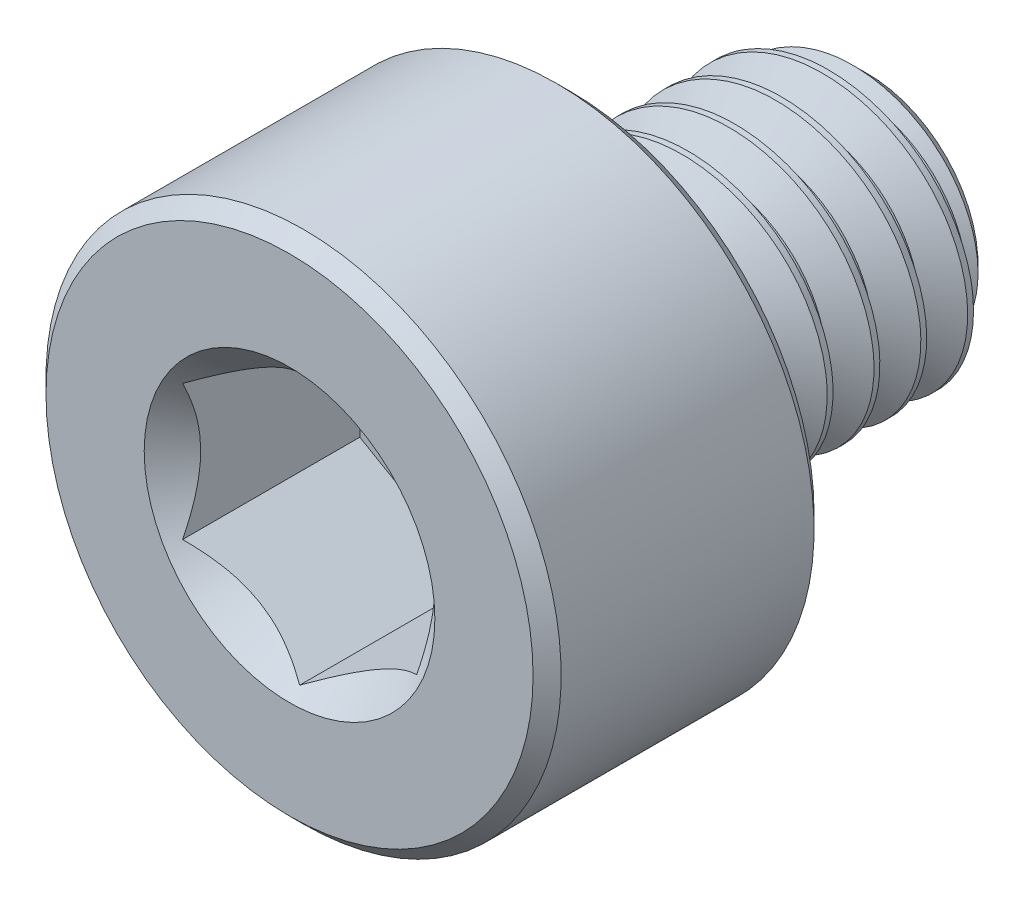
SolidWorks part; units mm, degrees
ref_plane "Front Plane" through (0, 0, 0) normal (0, 0, 1) x (1, 0, 0)
ref_plane "Top Plane" through (0, 0, 0) normal (0, 1, 0) x (1, 0, 0)
ref_plane "Right Plane" through (0, 0, 0) normal (1, 0, 0) x (0, 0, -1)
sketch "Sketch1" plane through (0, 0, 0) normal (1, 0, 0) x (0, 0, -1)
  line L0 (-3.0875, 0) -> (3.0875, 0) construction
  line L1 (3.0875, 0) -> (3.0875, 1.1752) construction
  line L2 (3.0875, 1.1752) -> (2.7627, 1.5) construction
  line L3 (2.7627, 1.5) -> (2.7125, 1.5) construction
  line L4 (2.7125, 1.5) -> (-0.0875, 1.5) construction
  line L5 (-0.0875, 1.5) -> (-0.0875, 2.75) construction
  line L6 (-0.0875, 2.75) -> (-3.0875, 2.75) construction
  line L7 (-3.0875, 2.75) -> (-3.0875, 0) construction
  line L8 (3.0875, 1.1752) -> (3.0875, 1.5) construction
  line L9 (3.0563, 1.5541) -> (3.3063, 1.1211) construction
  line L10 (3.3063, 1.1211) -> (3.5563, 1.5541) construction
  line L11 (3.5563, 1.5541) -> (3.0563, 1.5541) construction
  line L12 (3.3063, 1.5541) -> (3.3063, 1.5) construction
  line L13 (3.3063, 1.1211) -> (3.3063, 1.1752) construction
  line L14 (3.275, 1.1752) -> (3.3375, 1.1752) construction
  line L15 (3.0875, 1.5) -> (3.525, 1.5) construction
  line L16 (3.0719, 1.5271) -> (3.5406, 1.5271) construction
  line L17 (3.0875, 0) -> (3.0875, -1.5) construction
  line L18 (-0.2375, 2.75) -> (-0.0875, 2.6) construction
  line L19 (-2.9375, 2.75) -> (-3.0875, 2.6) construction
  line L20 (-0.0875, 1.5) -> (-0.0875, 0) construction
  line L21 (-0.0875, 0.75) -> (0.9708, 0.75) construction
  line L22 (0.9708, 0.75) -> (2.0292, 0.75) construction
  line L23 (2.0292, 0.75) -> (3.0875, 0.75) construction
  line L24 (0.9708, 0.75) -> (0.9708, 1.5) construction
  line L25 (0.9708, 1.5) -> (0.9708, 2.75) construction
  line L26 (2.0292, 0.75) -> (2.0292, 2.75) construction
  point P0 (-3.0875, 1.25)
  point P3 (1.8375, 1.5)
  point P4 (0, 0)
  point P18 (2.0292, 1.5)
  point P22 (3.3063, 1.1752)
  point P24 (2.7125, 1.5)
  point P25 (3.3063, 1.5)
  point P28 (3.3062, 1.5271)
  point P29 (1.8375, -1.5)
  point P30 (0.9708, 1.5)
  point P31 (-1.5875, 2.75)
  point P37 (-0.6125, 2.75)
  point P38 (-2.8625, 2.75)
  point P45 (0.9708, 0.75)
  point P46 (2.0292, 0.75)
  dimension "D2" = 0.0625
  dimension "D7" = 0.15
  dimension "D8" = 0.15
  dimension "D9" = 0.15
  dimension "D10" = 0.075
  dimension "D11" = 0.375
  dimension "Drive Size" = 2.5
  dimension "Head Diameter" = 5.5
  dimension "Head Height" = 3
  dimension "Thread Pitch" = 0.5
  dimension "Thread Dia" = 3
  dimension "Length" = 3.175
  dimension "D12" = 0.375
  dimension "D4" = 1.25
  dimension "D3" = 45
sketch "Sketch2" plane through (0, 0, 0) normal (1, 0, 0) x (0, 0, -1)
  line L0 (-3.0875, 0) -> (-3.0875, 2.6)
  line L1 (-2.9375, 2.75) -> (-0.2375, 2.75)
  line L2 (-0.0875, 2.6) -> (-0.0875, 1.65)
  line L4 (2.7627, 1.5) -> (3.0875, 1.1752)
  line L5 (3.0875, 1.1752) -> (3.0875, 0)
  line L6 (-0.0875, 2.75) -> (-3.0875, 2.75) construction
  line L7 (3.0875, 0) -> (-3.0875, 0)
  line L8 (-2.9375, 2.75) -> (-3.0875, 2.6) construction
  line L10 (-2.9375, 2.75) -> (-3.0875, 2.6)
  line L14 (-0.2375, 2.75) -> (-0.0875, 2.6) construction
  line L16 (-0.2375, 2.75) -> (-0.0875, 2.6)
  line L17 (-0.0875, 1.5) -> (-0.0875, 2.75) construction
  line L19 (0.0625, 1.5) -> (2.7627, 1.5)
  line L20 (2.7125, 1.5) -> (-0.0875, 1.5) construction
  arc A1 (-0.0875, 1.65) -> (0.0625, 1.5) centre (0.0625, 1.65) ccw
  dimension "D3" = 0.15
revolve "Revolve1" add sketch "Sketch2" angle 360 about L7
sketch "Sketch3" plane through (0, 0, 3.0875) normal (0, 0, 1) x (1, 0, 0)
  line L1 (1.25, -0.7217) -> (1.25, 0.7217)
  line L2 (1.25, 0.7217) -> (0, 1.4434)
  line L3 (0, 1.4434) -> (-1.25, 0.7217)
  line L4 (-1.25, 0.7217) -> (-1.25, -0.7217)
  line L5 (-1.25, -0.7217) -> (0, -1.4434)
  line L6 (0, -1.4434) -> (1.25, -0.7217)
  circle A0 centre (0, 0) radius 1.25 construction
  circle A1 centre (0, 0) radius 2.75 construction
  circle A2 centre (0, 0) radius 2.75 construction
  circle A3 centre (0, 0) radius 1.4434 construction
  point P13 (0, 0)
  dimension "D1" = 2.8868
extrude "Cut-Extrude1" cut sketch "Sketch3" against normal offset from surface (2 mm away) 1 up to face at (0, 2.6, 0.0875)
sketch "Sketch4" plane through (0, 0, 3.0875) normal (0, 0, 1) x (1, 0, 0)
  circle A0 centre (0, 0) radius 1.5516
  dimension "D1" = 3.1033
extrude "Cut-Extrude2" cut sketch "Sketch4" against normal up to vertex (1.5 mm away) draft 45 up to point (0, 2.75, 1.5875)
sketch "Sketch11" plane through (0, 0, 0) normal (1, 0, 0) x (0, 0, -1)
  line L0 (-3.0875, 0) -> (3.0875, 0) construction
  line L1 (-3.0875, 0) -> (3.0875, 0) construction
  line L2 (0.5078, 0) -> (0.5078, 1.5) construction
  line L3 (2.7125, 1.5) -> (-0.0875, 1.5) construction
  line L4 (2.4922, 0) -> (2.4922, 1.5) construction
  line L6 (3.0875, 1.1752) -> (3.0875, 1.5) construction
  point P2 (0.5078, 0)
  point P3 (2.4922, 0)
  dimension "D1" = 0.5953
  dimension "D2" = 0.5953
sketch "Sketch6" plane through (0, 0, -3.0875) normal (0, 0, -1) x (-1, 0, 0)
  circle A0 centre (0, 0) radius 1.5
curve "Helix/Spiral1" pitch 0.5 height 3.675 radius 1.5 centre (0, 0, -3.0875) axis (0, 0, 1) start towards (0, 1, 0)
sketch "Sketch10" plane through (0, 0, 0) normal (1, 0, 0) x (0, 0, -1)
  line L0 (0.0625, -2.75) -> (0.0625, 2.75)
  line L5 (-3.0875, 0) -> (3.0875, 0) construction
  line L6 (0.0625, 1.5) -> (0.0625, -1.5) construction
  point P3 (0.0625, 0)
split "Split1" trim tools "Sketch10" bodies to split 106 resulting bodies 114 115
sketch "Sketch7" plane through (0, 0, 0) normal (1, 0, 0) x (0, 0, -1)
  line L0 (3.0719, 1.5271) -> (3.5406, 1.5271)
  line L1 (3.5406, 1.5271) -> (3.3375, 1.1752)
  line L2 (3.3375, 1.1752) -> (3.275, 1.1752)
  line L3 (3.275, 1.1752) -> (3.0719, 1.5271)
sweep "Cut-Sweep1" cut profiles "Sketch7" path "Helix/Spiral1" align with end faces yes
sketch "Sketch8" plane through (0, 0, 0) normal (1, 0, 0) x (0, 0, -1)
  line L0 (-0.0875, 0) -> (-0.0875, 1.5)
  line L1 (0.0625, -1.5) -> (0.0625, 1.5) construction
  line L2 (-0.0875, 1.5) -> (0.0625, 1.5)
  line L4 (0.0625, 1.5) -> (0.9285, 0)
  line L5 (0.9285, 0) -> (-0.0875, 0)
  line L6 (2.7125, 1.5) -> (-0.0875, 1.5) construction
  line L7 (-3.0875, 0) -> (3.0875, 0) construction
  dimension "D1" = 60
revolve "Revolve2" add sketch "Sketch8" angle 360 about L5
equation "\"D2@Sketch1\" = \"Thread Pitch@Sketch1\" / 8"
equation "\"D4@Helix/Spiral1\" = \"Thread Pitch@Sketch1\""
equation "\"D7@Sketch1\" = \"Head Height@Sketch1\" * .05"
equation "\"D8@Sketch1\"=\"D7@Sketch1\""
equation "\"D9@Sketch1\"=\"D7@Sketch1\""
equation "\"D10@Sketch1\"=\"D7@Sketch1\"/2"
equation "\"D11@Sketch1\"=\"D10@Sketch1\"*5"
equation "\"D4@Sketch1\"=\"Thread Pitch@Sketch1\"*2.5"
equation "\"D12@Sketch1\"=\"Thread Pitch@Sketch1\"*.75"
equation "\"D3@Helix/Spiral1\"=\"Length@Sketch1\"+\"Thread Pitch@Sketch1\""
equation "\"D3@Sketch2\"=\"Thread Dia@Sketch1\"*0.05"
equation "\"D1@Sketch11\"=\"Length@Sketch1\"*0.1875"
equation "\"D2@Sketch11\"=\"D1@Sketch11\""
equation "\"D1@Sketch4\"=\"D1@Sketch3\"*1.075"
